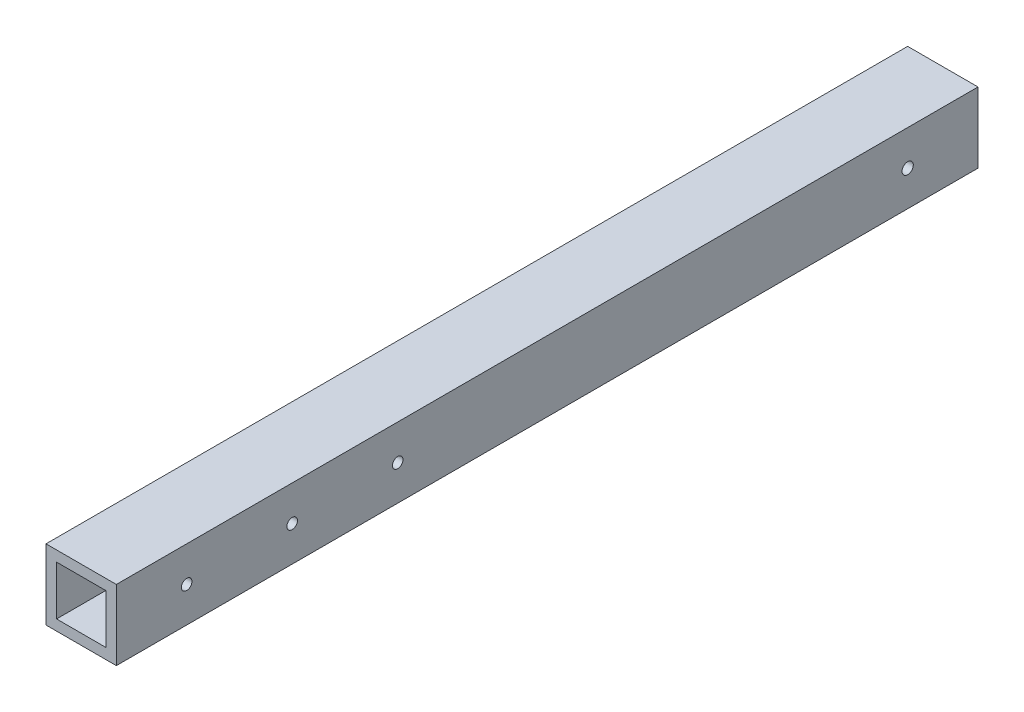
SolidWorks part; units mm, degrees
ref_plane "前视基准面" through (0, 0, 0) normal (0, 0, 1) x (1, 0, 0)
ref_plane "上视基准面" through (0, 0, 0) normal (0, 1, 0) x (1, 0, 0)
ref_plane "右视基准面" through (0, 0, 0) normal (1, 0, 0) x (0, 0, -1)
other "Configuration Table"
sketch "草图1" plane through (0, 0, 0) normal (0, 0, 1) x (1, 0, 0)
  line L0 (-9.3333, 11.0061) -> (-9.3333, -8.9939)
  line L1 (-9.3333, 11.0061) -> (10.6667, 11.0061)
  line L2 (-9.3333, -8.9939) -> (10.6667, -8.9939)
  line L3 (10.6667, 11.0061) -> (10.6667, -8.9939)
  dimension "D1" = 20
  dimension "D2" = 20
extrude "凸台-拉伸1" add sketch "草图1" along normal blind 245
sketch "草图2" plane through (0, 0, 0) normal (0, 0, -1) x (-1, 0, 0)
  line L0 (-10.6667, -8.9939) -> (-10.6667, 11.0061) construction
  line L1 (-7.6667, 8.0061) -> (6.3333, 8.0061)
  line L2 (-7.6667, 8.0061) -> (-7.6667, -5.9939)
  line L3 (-7.6667, -5.9939) -> (6.3333, -5.9939)
  line L4 (6.3333, 8.0061) -> (6.3333, -5.9939)
  line L5 (9.3333, 11.0061) -> (9.3333, -8.9939) construction
  line L6 (9.3333, -8.9939) -> (-10.6667, -8.9939) construction
  line L7 (-10.6667, 11.0061) -> (9.3333, 11.0061) construction
  dimension "D1" = 3
  dimension "D2" = 3
  dimension "D3" = 3
  dimension "D4" = 3
extrude "切除-拉伸1" cut sketch "草图2" against normal through all
sketch "草图3" plane through (-9.3333, 0, 0) normal (-1, 0, 0) x (0, 0, 1)
  circle A0 centre (225, 1.0061) radius 1.5
  circle A1 centre (195, 1.0061) radius 1.5
  circle A2 centre (165, 1.0061) radius 1.5
  circle A3 centre (20, 1.0061) radius 1.6
  dimension "D1" = 3.2
extrude "切除-拉伸2" cut sketch "草图3" against normal blind 80
